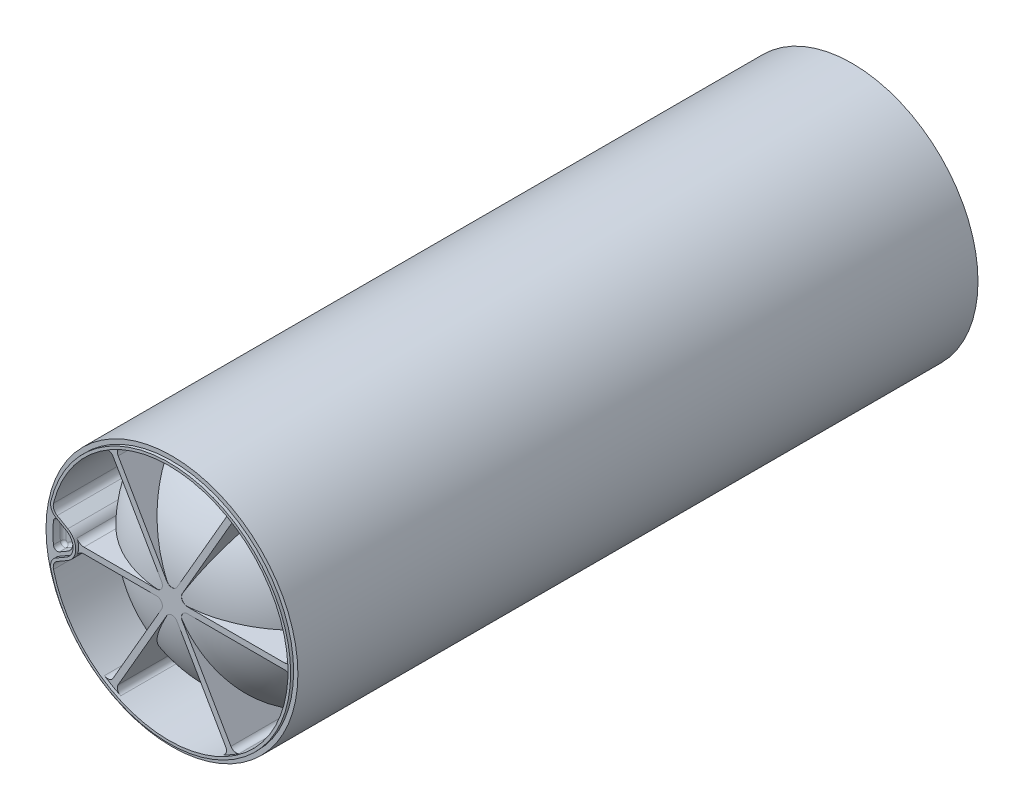
SolidWorks part; units mm, degrees
ref_plane "Front Plane" through (0, 0, 0) normal (0, 0, 1) x (1, 0, 0)
ref_plane "Top Plane" through (0, 0, 0) normal (0, 1, 0) x (1, 0, 0)
ref_plane "Right Plane" through (0, 0, 0) normal (1, 0, 0) x (0, 0, -1)
sketch "Sketch1" plane through (0, 0, 0) normal (0, 0, 1) x (1, 0, 0)
  circle A0 centre (-76.2, 0) radius 63.5
extrude "Boss-Extrude1" add sketch "Sketch1" along normal blind 342.9
fillet "Fillet1" radius 60 1 edges at (-12.7, 0, 342.9)
shell "Shell1" thickness 1.5875 removed face at (-12.7, 0, 0)
sketch "Sketch8" plane through (0, 0, 342.9) normal (0, 0, 1) x (1, 0, 0)
  line L0 (-76.2, 0) -> (12.7444, 0) construction
  line L1 (-76.1912, 0.0152) -> (24923.8088, 43301.2854) construction
  line L2 (-75.2371, -1.6677) -> (24924.7629, -43302.9379) construction
  line L3 (-131.2, 0) -> (24868.8, 43301.2702) construction
  line L4 (-130.6834, -0.8948) -> (24869.3166, -43302.165) construction
  line L5 (737.3254, -495.6699) -> (-43429.9702, 25004.3301) construction
  line L6 (-128.7, -4.3301) -> (43172.5702, 24995.6699) construction
  line L7 (-120.5346, -1.5) -> (-83.9942, -1.5)
  line L8 (-105.9101, 48.4594) -> (-81.3962, 6)
  line L9 (-103.312, -49.9594) -> (-78.7981, -7.5)
  line L10 (-120.5346, 1.5) -> (-83.9942, 1.5)
  line L11 (-103.312, 49.9594) -> (-78.7981, 7.5)
  line L12 (-105.9101, -48.4594) -> (-81.3962, -6)
  line L13 (-76.5362, -2.4177) -> (24923.4638, -43303.6879) construction
  line L14 (-73.9381, -0.9177) -> (24926.0619, -43302.1879) construction
  line L15 (-77.4903, 0.7652) -> (24922.5097, 43302.0354) construction
  line L16 (-74.8922, -0.7348) -> (24925.1078, 43300.5354) construction
  line L17 (-76.2, 1.5) -> (12.7444, 1.5) construction
  line L18 (-76.2, -1.5) -> (12.7444, -1.5) construction
  line L21 (-127.2, 6.9282) -> (-132.5527, 10.0186)
  line L22 (-132.5527, -10.0186) -> (-127.2, -6.9282)
  line L23 (-127.2, -6.9282) -> (43174.0702, 24993.0718) construction
  line L24 (738.8254, -493.0718) -> (-43428.4702, 25006.9282) construction
  line L25 (-73.6019, 7.5) -> (-49.088, 49.9594)
  line L26 (-68.4058, 1.5) -> (-19.3779, 1.5)
  line L27 (-71.0038, -6) -> (-46.4899, -48.4594)
  line L28 (-71.0038, 6) -> (-46.4899, 48.4594)
  line L29 (-68.4058, -1.5) -> (-19.3779, -1.5)
  line L30 (-73.6019, -7.5) -> (-49.088, -49.9594)
  circle A0 centre (-76.2, 0) radius 63.5 construction
  circle A1 centre (-76.2, 0) radius 63.5
  arc A2 (-110.2086, 49.4309) -> (-134.435, 14.4457) centre (-76.2, 0) ccw
  circle A3 centre (-76.2, 0) radius 55 construction
  circle A4 centre (-131.2, 0) radius 5 construction
  arc A5 (-50.3959, 54.1678) -> (-102.0041, 54.1678) centre (-76.2, 0) ccw
  arc A6 (-16.3873, 4.7368) -> (-42.1914, 49.4309) centre (-76.2, 0) ccw
  arc A7 (-42.1914, -49.4309) -> (-16.3873, -4.7368) centre (-76.2, 0) ccw
  arc A8 (-102.0041, -54.1678) -> (-50.3959, -54.1678) centre (-76.2, 0) ccw
  arc A9 (-134.435, -14.4457) -> (-110.2086, -49.4309) centre (-76.2, 0) ccw
  arc A11 (-124.0898, 3.6667) -> (-127.2, 6.9282) centre (-131.2, 0) ccw
  arc A13 (-127.2, -6.9282) -> (-124.0898, -3.6667) centre (-131.2, 0) ccw
  arc A14 (-134.435, -14.4457) -> (-132.5527, -10.0186) centre (-130.5527, -13.4827) cw
  arc A15 (-120.5346, -1.5) -> (-124.0898, -3.6667) centre (-120.5346, -5.5) ccw
  arc A16 (-120.5346, 1.5) -> (-124.0898, 3.6667) centre (-120.5346, 5.5) cw
  arc A17 (-132.5527, 10.0186) -> (-134.435, 14.4457) centre (-130.5527, 13.4827) cw
  arc A18 (-110.2086, -49.4309) -> (-105.9101, -48.4594) centre (-108.5082, -46.9594) ccw
  arc A19 (-102.0041, -54.1678) -> (-103.312, -49.9594) centre (-100.7139, -51.4594) cw
  arc A20 (-50.3959, -54.1678) -> (-49.088, -49.9594) centre (-51.6861, -51.4594) ccw
  arc A21 (-42.1914, -49.4309) -> (-46.4899, -48.4594) centre (-43.8918, -46.9594) cw
  arc A22 (-16.3873, -4.7368) -> (-19.3779, -1.5) centre (-19.3779, -4.5) ccw
  arc A23 (-19.3779, 1.5) -> (-16.3873, 4.7368) centre (-19.3779, 4.5) ccw
  arc A24 (-42.1914, 49.4309) -> (-46.4899, 48.4594) centre (-43.8918, 46.9594) ccw
  arc A25 (-49.088, 49.9594) -> (-50.3959, 54.1678) centre (-51.6861, 51.4594) ccw
  arc A26 (-103.312, 49.9594) -> (-102.0041, 54.1678) centre (-100.7139, 51.4594) cw
  arc A27 (-105.9101, 48.4594) -> (-110.2086, 49.4309) centre (-108.5082, 46.9594) ccw
  arc A30 (-83.9942, -1.5) -> (-81.3962, -6) centre (-83.9942, -4.5) cw
  arc A31 (-78.7981, -7.5) -> (-73.6019, -7.5) centre (-76.2, -9) cw
  arc A32 (-71.0038, -6) -> (-68.4058, -1.5) centre (-68.4058, -4.5) cw
  arc A33 (-68.4058, 1.5) -> (-71.0038, 6) centre (-68.4058, 4.5) cw
  arc A34 (-73.6019, 7.5) -> (-78.7981, 7.5) centre (-76.2, 9) cw
  arc A35 (-83.9942, 1.5) -> (-81.3962, 6) centre (-83.9942, 4.5) ccw
  dimension "D1" = 1.5
  dimension "D3" = 3
  dimension "D5" = 4
  dimension "D6" = 3
  dimension "D7" = 3
  dimension "D2" = 1.5
  dimension "D4" = 3
extrude "Boss-Extrude6" add sketch "Sketch8" against normal up to body
sketch "Sketch11" plane through (0, 0, 342.9) normal (0, 0, 1) x (1, 0, 0)
  line L0 (-249.2763, -302.8263) -> (-160.332, -302.8263) construction
  line L1 (-127.2, -6.9282) -> (-132.5527, -10.0186) construction
  line L2 (-248.3135, -304.494) -> (24751.6865, -43605.7642) construction
  line L4 (-303.7597, -303.7211) -> (24696.2403, -43604.9913) construction
  line L5 (564.2491, -798.4961) -> (-43603.0465, 24701.5039) construction
  line L6 (-301.7763, -307.1564) -> (42999.4939, 24692.8436) construction
  line L7 (-132.5527, 10.0186) -> (-127.2, 6.9282) construction
  line L8 (-132.5527, 10.0186) -> (-127.2, 6.9282) construction
  line L9 (-132.9782, 6.8001) -> (-128.7, 4.3301)
  line L10 (-134.0527, 7.4205) -> (-128.7, 4.3301) construction
  line L14 (-128.7, -4.3301) -> (-132.9782, -6.8001)
  arc A0 (-134.435, -14.4457) -> (-110.2086, -49.4309) centre (-76.2, 0) ccw construction
  arc A1 (-135.9705, 5.2428) -> (-135.9705, -5.2428) centre (-76.2, 0) ccw
  arc A2 (-128.7, 4.3301) -> (-128.7, -4.3301) centre (-131.2, 0) cw
  arc A3 (-132.9782, 6.8001) -> (-135.9705, 5.2428) centre (-133.9782, 5.0681) ccw
  arc A4 (-135.9705, -5.2428) -> (-132.9782, -6.8001) centre (-133.9782, -5.0681) ccw
  dimension "D2" = 3
  dimension "D3" = 5
  dimension "D4" = 2
  dimension "D1" = 3
extrude "Cut-Extrude1" cut sketch "Sketch11" against normal blind 5 contours L14 A4 A1 A3 L9 A2
sketch "Sketch12" plane through (0, 0, 337.9) normal (0, 0, 1) x (1, 0, 0)
  circle A0 centre (-131.2, 0) radius 2
extrude "Cut-Extrude2" cut sketch "Sketch12" against normal blind 30
sketch "Sketch13" plane through (0, 0, 0) normal (0, 0, -1) x (-1, 0, 0)
  arc A1 (132.4711, 1.5442) -> (132.4711, -1.5442) centre (131.2, 0) ccw construction
  arc A2 (132.4711, 1.5442) -> (132.4711, -1.5442) centre (131.2, 0) ccw construction
  circle A3 centre (131.2, 0) radius 4
extrude "Cut-Extrude3" cut sketch "Sketch13" against normal blind 327.56
sketch "Sketch9" plane through (0, 0, 342.9) normal (0, 0, 1) x (1, 0, 0)
  line L0 (-132.5527, 10.0186) -> (-127.2, 6.9282) construction
  line L1 (-127.2, -6.9282) -> (-132.5527, -10.0186) construction
  line L2 (-132.5527, 10.0186) -> (-127.2, 6.9282)
  line L3 (-127.2, -6.9282) -> (-132.5527, -10.0186)
  line L4 (-133.2277, 8.8495) -> (-127.875, 5.7591)
  line L5 (-127.875, -5.7591) -> (-133.2277, -8.8495)
  arc A0 (-134.435, -14.4457) -> (-134.435, 14.4457) centre (-76.2, 0) ccw
  arc A1 (-135.7453, -14.7708) -> (-135.7453, 14.7708) centre (-76.2, 0) ccw
  arc A2 (-134.435, 14.4457) -> (-132.5527, 10.0186) centre (-130.5527, 13.4827) ccw construction
  arc A3 (-127.2, -6.9282) -> (-124.0898, -3.6667) centre (-131.2, 0) ccw construction
  arc A4 (-132.5527, -10.0186) -> (-134.435, -14.4457) centre (-130.5527, -13.4827) ccw construction
  arc A5 (-134.435, 14.4457) -> (-132.5527, 10.0186) centre (-130.5527, 13.4827) ccw
  arc A6 (-127.2, -6.9282) -> (-127.2, 6.9282) centre (-131.2, 0) ccw
  arc A7 (-132.5527, -10.0186) -> (-134.435, -14.4457) centre (-130.5527, -13.4827) ccw
  arc A8 (-135.7453, 14.7708) -> (-133.2277, 8.8495) centre (-130.5527, 13.4827) ccw
  arc A9 (-127.875, -5.7591) -> (-127.875, 5.7591) centre (-131.2, 0) ccw
  arc A10 (-133.2277, -8.8495) -> (-135.7453, -14.7708) centre (-130.5527, -13.4827) ccw
  point P1 (-136.7576, -23.4339)
  point P3 (-134.3819, -22.9053)
  point P13 (-136.0096, -38.3425)
  point P16 (0, 0)
  dimension "D1" = 1.35
extrude "Boss-Extrude7" add sketch "Sketch9" along normal blind 1.5
fillet "Fillet2" radius 1.5 7 edges at (-130.8391, -5.5651, 337.9) (-126.2, 0, 337.9) (-130.8391, 5.5651, 337.9) (-134.9014, 6.8422, 337.9) (-136.2, 0, 337.9) (-134.9014, -6.8422, 337.9) (-135.2, 0, 327.56)
